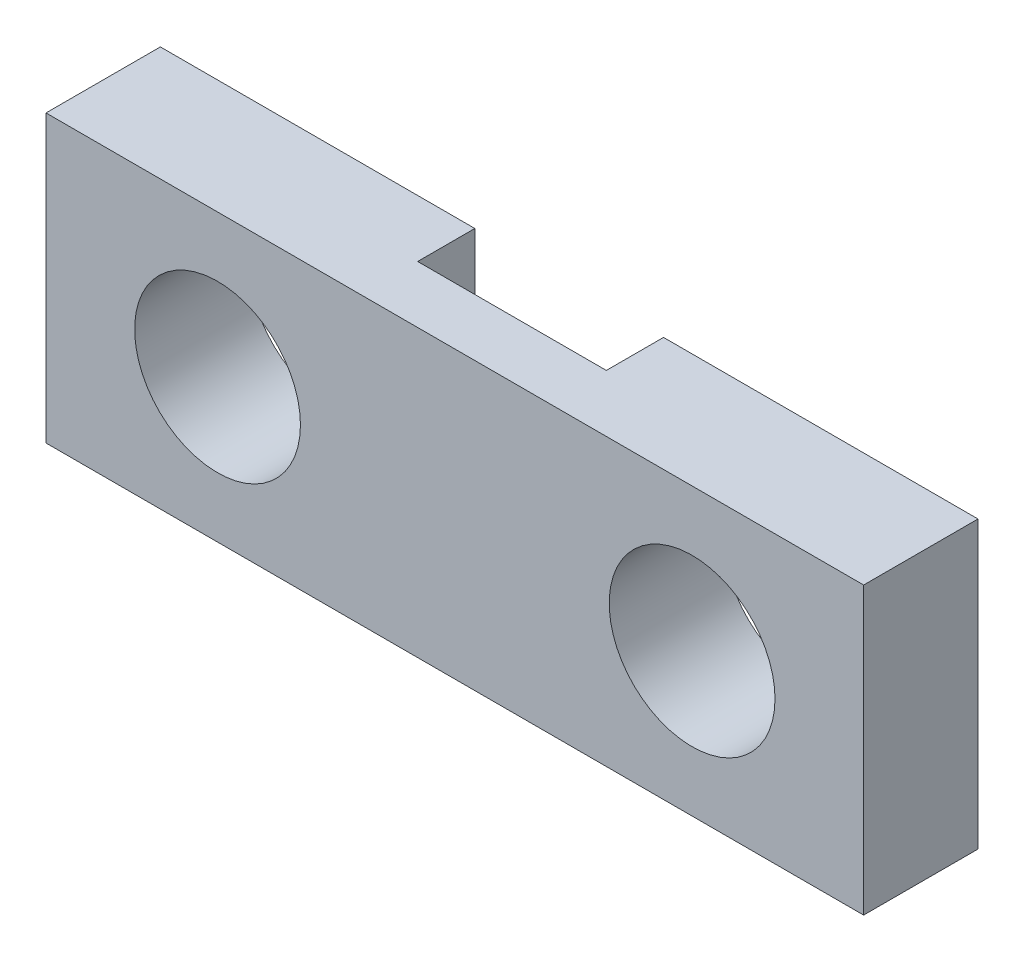
SolidWorks part; units mm, degrees
ref_plane "Front Plane" through (0, 0, 0) normal (1, 0, 0) x (0, 1, 0)
ref_plane "Top Plane" through (0, 0, 0) normal (0, 0, 1) x (0, 1, 0)
ref_plane "Right Plane" through (0, 0, 0) normal (0, 1, 0) x (-1, 0, 0)
sketch "Sketch2" plane through (0, 0, 0) normal (0, 0, 1) x (0, 1, 0)
  line L0 (0, -4.15) -> (0, 4.15) construction
  line L2 (-2.5, -7.15) -> (2.5, -7.15)
  line L3 (-2.5, -7.15) -> (-2.5, 7.15)
  line L4 (-2.5, 7.15) -> (2.5, 7.15)
  line L5 (2.5, -7.15) -> (2.5, 7.15)
  line L6 (-2.5, -7.15) -> (2.5, 7.15) construction
  line L7 (-2.5, 7.15) -> (2.5, -7.15) construction
  line L8 (-2.5, -1.65) -> (2.5, -1.65)
  line L9 (-2.5, -1.65) -> (-2.5, 1.65)
  line L10 (-2.5, 1.65) -> (2.5, 1.65)
  line L11 (2.5, -1.65) -> (2.5, 1.65)
  line L12 (-2.5, -1.65) -> (2.5, 1.65) construction
  line L13 (-2.5, 1.65) -> (2.5, -1.65) construction
  point P0 (0, 0)
  point P4 (0, 0)
  point P10 (0, 0)
  point P15 (2.4953, 1.7214)
  dimension "D1" = 8.3
  dimension "D2" = 3.3
  dimension "D3" = 3
  dimension "D4" = 5
extrude "Boss-Extrude1" add sketch "Sketch2" along normal blind 2 contours L5 L4 L3 L2
extrude "Cut-Extrude1" cut sketch "Sketch2<4>" along normal blind 1 contours L8 L11 L10 L9
sketch "Sketch2<4>" plane through (0, 0, 0) normal (0, 0, 1) x (0, 1, 0) same geometry as "Sketch2"
hole_wizard "M2.5 Clearance Hole1" positions "Sketch3" profile "Sketch4" hole size "M2.5" standard "ANSI Metric" end condition through all
sketch "Sketch3" plane through (0, 0, 2) normal (0, 0, 1) x (1, 0, 0)
  point P0 (-4.15, 0)
  point P3 (4.15, 0)
sketch "Sketch4" plane through (-4.15, 0, 2) normal (1, 0, 0) x (0, -1, 0)
  line L0 (0, 0) -> (0, 2)
  line L1 (0, 2) -> (1.45, 2)
  line L2 (1.45, 2) -> (1.45, 0)
  line L5 (1.45, 0) -> (0, 0)
  line L11 (0, -6.35) -> (0, 107.95) construction
  dimension "Thru Hole Dia." = 2.9
  dimension "Thru Hole Depth" = 2
